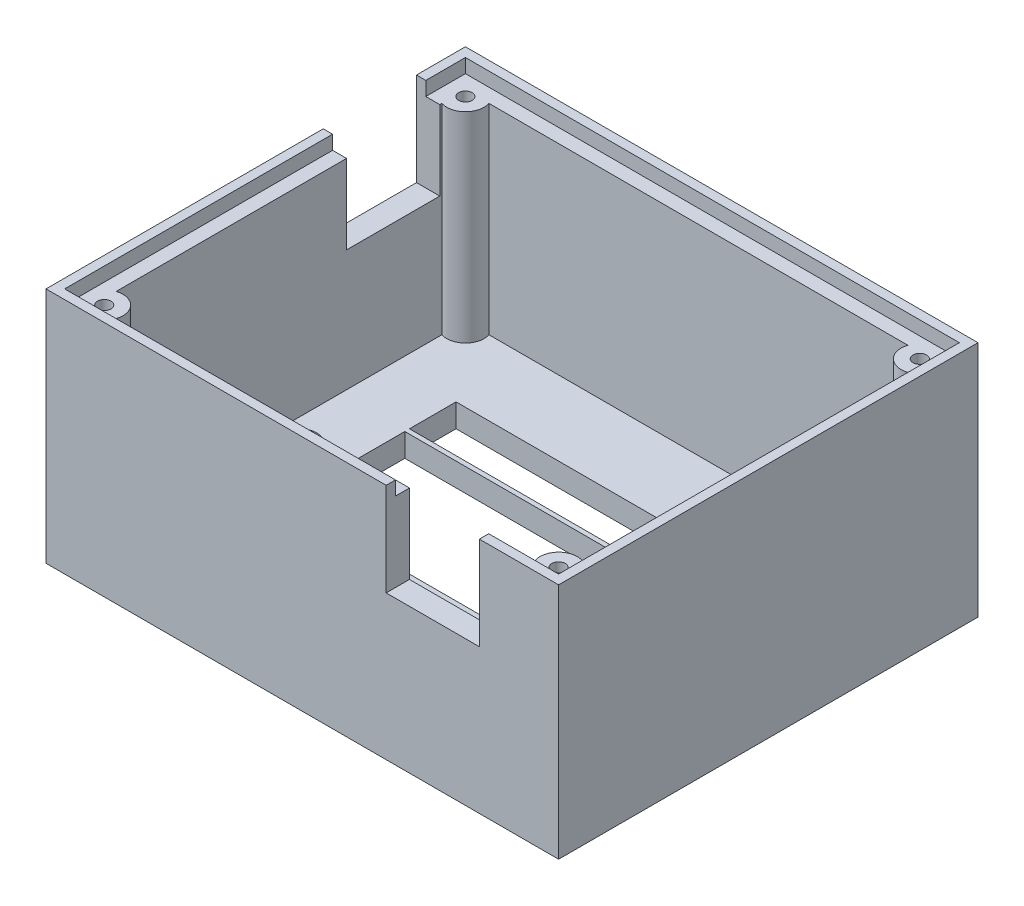
SolidWorks part; units mm, degrees
ref_plane "Front Plane" through (0, 0, 0) normal (0, 0, 1) x (1, 0, 0)
ref_plane "Top Plane" through (0, 0, 0) normal (0, 1, 0) x (1, 0, 0)
ref_plane "Right Plane" through (0, 0, 0) normal (1, 0, 0) x (0, 0, -1)
sketch "Sketch1" plane through (0, 0, 0) normal (0, 1, 0) x (1, 0, 0)
  line L1 (-55, -45) -> (55, -45)
  line L2 (-55, -45) -> (-55, 45)
  line L3 (-55, 45) -> (55, 45)
  line L4 (55, -45) -> (55, 45)
extrude "Boss-Extrude1" add sketch "Sketch1" along normal blind 51
sketch "Sketch2" plane through (0, 51, 0) normal (0, 1, 0) x (1, 0, 0)
  line L1 (-50, 40) -> (50, 40)
  line L2 (-50, 40) -> (-50, -40)
  line L3 (-50, -40) -> (50, -40)
  line L4 (50, 40) -> (50, -40)
extrude "Cut-Extrude1" cut sketch "Sketch2" against normal blind 46
sketch "Sketch3" plane through (0, 51, 0) normal (0, 1, 0) x (1, 0, 0)
  line L1 (-53, 43) -> (53, 43)
  line L2 (-53, 43) -> (-53, 40)
  line L3 (-53, 40) -> (53, 40)
  line L4 (53, 43) -> (53, 40)
extrude "Cut-Extrude2" cut sketch "Sketch3" against normal blind 3
sketch "Sketch5" plane through (0, 51, 0) normal (0, 1, 0) x (1, 0, 0)
  line L1 (53, 40) -> (50, 40)
  line L2 (53, 40) -> (53, -43)
  line L3 (53, -43) -> (50, -43)
  line L4 (50, 40) -> (50, -43)
extrude "Cut-Extrude3" cut sketch "Sketch5" against normal blind 3
sketch "Sketch6" plane through (0, 51, 0) normal (0, 1, 0) x (1, 0, 0)
  line L1 (50, -43) -> (-53, -43)
  line L2 (50, -43) -> (50, -40)
  line L3 (50, -40) -> (-53, -40)
  line L4 (-53, -43) -> (-53, -40)
extrude "Cut-Extrude4" cut sketch "Sketch6" against normal blind 3
sketch "Sketch7" plane through (0, 51, 0) normal (0, 1, 0) x (1, 0, 0)
  line L1 (-53, 40) -> (-50, 40)
  line L2 (-53, 40) -> (-53, -40)
  line L3 (-53, -40) -> (-50, -40)
  line L4 (-50, 40) -> (-50, -40)
extrude "Cut-Extrude5" cut sketch "Sketch7" against normal blind 3
sketch "Sketch9" plane through (0, 5, 0) normal (0, 1, 0) x (1, 0, 0)
  circle A0 centre (-48.75, 38.75) radius 4
extrude "Boss-Extrude2" add sketch "Sketch9" along normal blind 43 contours A0
sketch "Sketch10" plane through (0, 5, 0) normal (0, 1, 0) x (1, 0, 0)
  circle A0 centre (48.75, 38.75) radius 4
  circle A1 centre (48.75, -38.75) radius 4
  circle A2 centre (-48.75, -38.75) radius 4
extrude "Boss-Extrude3" add sketch "Sketch10" along normal blind 43
hole_wizard "M2.5 Clearance Hole1" positions "Sketch11" profile "Sketch12" hole size "M2.5" standard "ANSI Metric"
sketch "Sketch11" plane through (0, 48, 0) normal (0, 1, 0) x (1, 0, 0)
  point P0 (-48.75, 38.75)
  point P3 (48.75, 38.75)
  point P6 (48.75, -38.75)
  point P9 (-48.75, -38.75)
  point P12 (0, 0)
  point P13 (0, 0)
  point P14 (0, 0)
  point P15 (0, 0)
sketch "Sketch12" plane through (-48.75, 48, -38.75) normal (1, 0, 0) x (0, 0, 1)
  line L0 (0, 0) -> (0, 5.8712)
  line L1 (0, 5.8712) -> (1.45, 5)
  line L2 (1.45, 5) -> (1.45, 0)
  line L5 (1.45, 0) -> (0, 0)
  line L10 (0, 5.8712) -> (-1.45, 5) construction
  line L11 (0, -6.35) -> (0, 107.95) construction
  dimension "Hole Dia." = 2.9
  dimension "Hole Depth" = 5
  dimension "Drill Angle" = 118
sketch "Sketch14" plane through (-55, 0, 0) normal (-1, 0, 0) x (0, 0, 1)
  line L1 (-34.5, 51) -> (-14.5, 51)
  line L2 (-34.5, 51) -> (-34.5, 31)
  line L3 (-34.5, 31) -> (-14.5, 31)
  line L4 (-14.5, 51) -> (-14.5, 31)
  point P4 (0, 0)
  point P5 (0, 0)
  point P6 (0, 0)
  point P7 (0, 0)
extrude "Cut-Extrude6" cut sketch "Sketch14" against normal blind 5
sketch "Sketch15" plane through (0, 0, 45) normal (0, 0, 1) x (1, 0, 0)
  line L1 (38, 51) -> (18, 51)
  line L2 (38, 51) -> (38, 31)
  line L3 (38, 31) -> (18, 31)
  line L4 (18, 51) -> (18, 31)
  point P4 (0, 0)
  point P5 (0, 0)
  point P6 (0, 0)
  point P7 (0, 0)
  point P8 (0, 0)
  point P9 (0, 0)
  point P10 (0, 0)
  point P11 (0, 0)
  point P12 (0, 0)
extrude "Cut-Extrude7" cut sketch "Sketch15" against normal blind 5
sketch "Sketch16" plane through (0, 5, 0) normal (0, 1, 0) x (1, 0, 0)
  line L1 (36, 13) -> (-36, 13)
  line L2 (36, 13) -> (36, -13)
  line L3 (36, -13) -> (-36, -13)
  line L4 (-36, 13) -> (-36, -13)
extrude "Cut-Extrude8" cut sketch "Sketch16" against normal blind 5
sketch "Sketch17" plane through (0, 0, 0) normal (0, -1, 0) x (1, 0, 0)
  line L1 (-36, -14) -> (36, -14)
  line L2 (-36, -14) -> (-36, -24)
  line L3 (-36, -24) -> (36, -24)
  line L4 (36, -14) -> (36, -24)
extrude "Cut-Extrude9" cut sketch "Sketch17" against normal blind 5
hole_wizard "M6 Clearance Hole1" positions "Sketch18" profile "Sketch19" hole size "M6" standard "ANSI Metric" end condition through all
sketch "Sketch18" plane through (0, 0, 0) normal (0, -1, 0) x (-1, 0, 0)
  point P0 (45.2228, 0)
sketch "Sketch19" plane through (-45.2228, 0, 0) normal (1, 0, 0) x (0, 0, -1)
  line L0 (0, 0) -> (0, 51)
  line L1 (0, 51) -> (3.3, 51)
  line L2 (3.3, 51) -> (3.3, 0)
  line L5 (3.3, 0) -> (0, 0)
  line L11 (0, -6.35) -> (0, 107.95) construction
  dimension "Thru Hole Dia." = 6.6
  dimension "Thru Hole Depth" = 51
